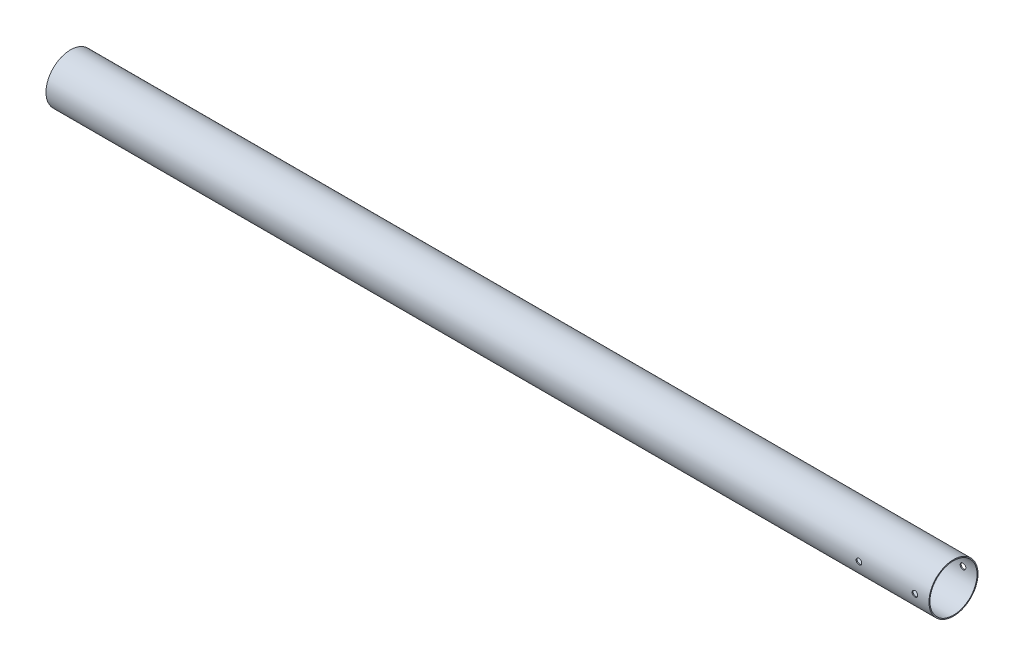
SolidWorks part; units mm, degrees
ref_plane "Front" through (0, 0, 0) normal (0, 0, 1) x (1, 0, 0)
ref_plane "Top" through (0, 0, 0) normal (0, 1, 0) x (1, 0, 0)
ref_plane "Right" through (0, 0, 0) normal (1, 0, 0) x (0, 0, -1)
sketch "Sketch1" plane through (0, 0, 0) normal (1, 0, 0) x (0, 0, -1)
  line L0 (21.336, 0) -> (22.225, 0) construction
  line L1 (21.336, 0) -> (22.225, 0) construction
  line L2 (21.7805, 0) -> (21.7805, 1.0672) construction
  circle A0 centre (0, 0) radius 22.225
  circle A1 centre (0, 0) radius 21.336
  point P4 (22.225, 0)
  point P5 (21.336, 0)
  dimension "OD" = 44.45
  dimension "ID" = 42.672
  dimension "Wall Thickness" = 0.889
sketch "Sketch2" plane through (0, 0, 0) normal (0, 0, 1) x (1, 0, 0)
  line L0 (-400.05, 0) -> (400.05, 0) construction
  point P2 (-344.4875, 0)
  point P3 (344.4875, 0)
  dimension "D1" = 55.5625
  dimension "D2" = 55.5625
sketch "Sketch3" plane through (0, 0, 0) normal (1, 0, 0) x (0, 0, -1)
  circle A0 centre (0, 0) radius 21.336 construction
  circle A1 centre (0, 0) radius 22.225 construction
  circle A2 centre (0, 0) radius 21.336
  circle A3 centre (0, 0) radius 22.225
extrude "Boss-Extrude1" add sketch "Sketch3" along normal mid plane 800.1
sketch "Sketch4" plane through (0, 0, 0) normal (0, 0, 1) x (1, 0, 0)
  line L0 (400.05, 0) -> (336.55, 0) construction
  line L7 (400.05, -22.225) -> (400.05, 22.225) construction
  circle A0 centre (336.55, 0) radius 2.5527
  circle A1 centre (387.35, 0) radius 2.5527
  dimension "D3" = 63.5
  dimension "D1" = 5.1054
  dimension "D2" = 12.7
extrude "Cut-Extrude1" cut sketch "Sketch4" along normal through all both and the other way through all
equation "\"D1@Boss-Extrude1\"=\"Length@Sketch2\""
equation "\"D1@Sketch2\"=\"OD@Sketch1\"*1.25"
equation "\"D2@Sketch2\"=\"D1@Sketch2\""
